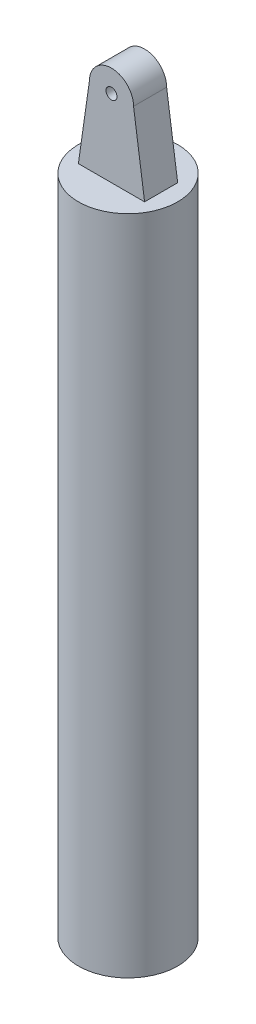
SolidWorks part; units mm, degrees
material "Hexcel AS4C (3000 Filaments)"
ref_plane "Front Plane" through (0, 0, 0) normal (0, 0, 1) x (1, 0, 0)
ref_plane "Top Plane" through (0, 0, 0) normal (0, 1, 0) x (1, 0, 0)
ref_plane "Right Plane" through (0, 0, 0) normal (1, 0, 0) x (0, 0, -1)
sketch "Sketch1" plane through (0, 0, 0) normal (0, 0, 1) x (1, 0, 0)
  line L0 (-10, 0) -> (-15, -35)
  line L1 (-15, -35) -> (15, -35)
  line L2 (15, -35) -> (10, 0)
  circle A0 centre (0, 0) radius 10
  circle A1 centre (0, 0) radius 2.5
  dimension "D1" = 5
  dimension "D2" = 20
  dimension "D3" = 30
  dimension "D4" = 35
extrude "Boss-Extrude1" add sketch "Sketch1" along normal blind 15 contours A0 L0 L1 L2 | A0 A1 region at (0, -21.8223, 0) region at (0, 9.7172, 0)
sketch "Sketch2" plane through (0, -35, 0) normal (0, -1, 0) x (1, 0, 0)
  circle A0 centre (0, 7.5) radius 22.5
  dimension "D2" = 45
  dimension "D1" = 7.5
extrude "Boss-Extrude2" add sketch "Sketch2" along normal blind 250
sketch "Sketch3" plane through (0, -285, 0) normal (0, -1, 0) x (1, 0, 0)
  circle A0 centre (0, 7.5) radius 22.5
  circle A1 centre (0, 7.5) radius 20
  dimension "D1" = 40
  dimension "D2" = 45
  dimension "D3" = 7.5
extrude "Boss-Extrude3" add sketch "Sketch3" along normal blind 50
sketch "Sketch4" plane through (0, -335, 0) normal (0, -1, 0) x (1, 0, 0)
  circle A0 centre (0, 7.5) radius 20
  dimension "D1" = 40
curve "Helix/Spiral1" pitch 2 height 44 radius 20 centre (0, -335, 7.5) axis (0, 1, 0) start towards (0, 0, -1)
ref_plane "Plane1" through (-20, -335, 7.5) normal (0, 0.0159, 0.9999) x (1, 0, 0)
sketch "Sketch5" plane through (-20, -335, 7.5) normal (0, 0.0159, 0.9999) x (1, 0, 0)
  line L1 (-1.4, 0.0033) -> (0.6971, -1.2141)
  line L2 (0.6971, -1.2141) -> (0.7029, 1.2108)
  line L3 (0.7029, 1.2108) -> (-1.4, 0.0033)
  circle A0 centre (0, 0) radius 0.7 construction
  dimension "D1" = 1.4
sweep "Cut-Sweep1" cut profiles "Sketch5" path "Helix/Spiral1" align with end faces yes
